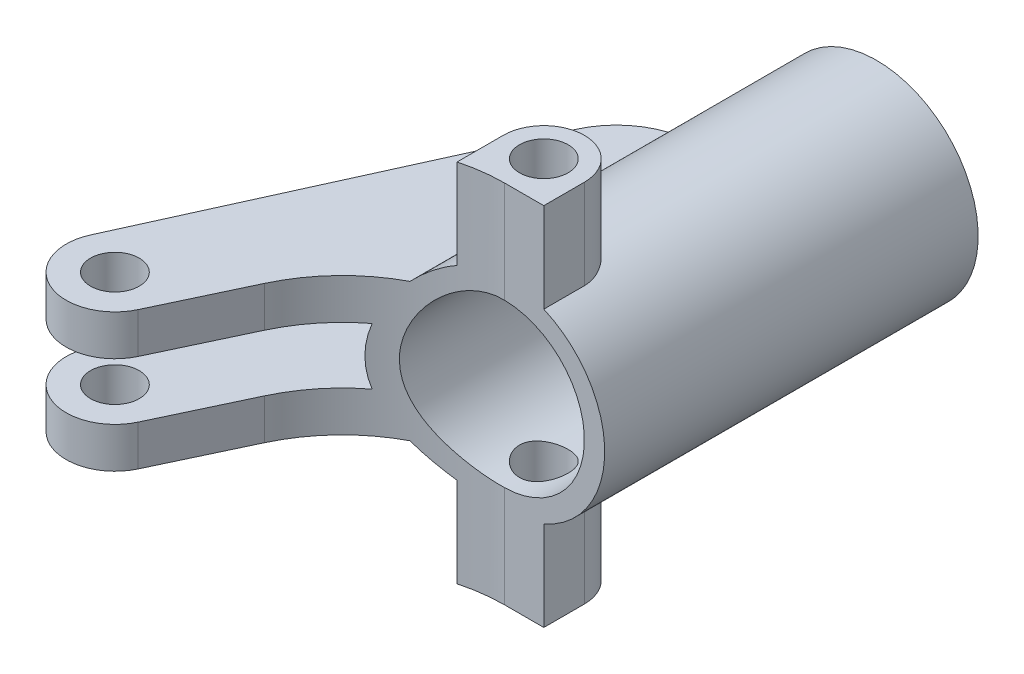
SolidWorks part; units mm, degrees
ref_plane "Alzado" through (0, 0, 0) normal (0, 0, 1) x (1, 0, 0)
ref_plane "Planta" through (0, 0, 0) normal (0, 1, 0) x (1, 0, 0)
ref_plane "Vista lateral" through (0, 0, 0) normal (1, 0, 0) x (0, 0, -1)
sketch "Croquis1" plane through (0, 0, 0) normal (0, 0, 1) x (1, 0, 0)
  circle A0 centre (0, 0) radius 6.25
  circle A1 centre (0, 0) radius 5
  dimension "D1" = 12.5
  dimension "D2" = 10
extrude "Saliente-Extruir1" add sketch "Croquis1" along normal blind 15
ref_plane "Plano1" through (0, 6.25, 0) normal (0, 1, 0) x (1, 0, 0)
ref_plane "Plano2" through (0, 11.25, 0) normal (0, 1, 0) x (1, 0, 0)
ref_plane "Plano3" through (0, -11.25, 0) normal (0, 1, 0) x (1, 0, 0)
sketch "Croquis2" plane through (0, 11.25, 0) normal (0, 1, 0) x (1, 0, 0)
  line L0 (0, -15) -> (0, -8.2224) construction
  line L1 (-6.25, -15) -> (6.25, -15) construction
  line L2 (-2.5, -15) -> (-2.5, -10)
  line L3 (-2.5, -10) -> (2.5, -10)
  line L4 (2.5, -10) -> (2.5, -15)
  line L5 (2.5, -15) -> (-2.5, -15)
  dimension "D1" = 5
  dimension "D2" = 5
extrude "Saliente-Extruir2" add sketch "Croquis2" against normal up to next
sketch "Croquis3" plane through (0, -11.25, 0) normal (0, 1, 0) x (1, 0, 0)
  line L0 (-2.5, -15) -> (2.5, -15) construction
  line L1 (2.5, -15) -> (2.5, -10) construction
  line L2 (-2.5, -10) -> (-2.5, -15) construction
  line L3 (2.5, -10) -> (-2.5, -10) construction
  line L4 (-2.5, -15) -> (2.5, -15)
  line L5 (2.5, -15) -> (2.5, -10)
  line L6 (-2.5, -10) -> (-2.5, -15)
  line L7 (2.5, -10) -> (-2.5, -10)
extrude "Saliente-Extruir3" add sketch "Croquis3" along normal up to next
sketch "Croquis4" plane through (0, 11.25, 0) normal (0, 1, 0) x (1, 0, 0)
  line L0 (-2.5, -12.5) -> (3.9489, -12.5) construction
  line L1 (-2.5, -10) -> (-2.5, -15) construction
  line L2 (0, -8.736) -> (0, -17.4365) construction
  circle A0 centre (0, -12.5) radius 1.5
  dimension "D1" = 3
extrude "Cortar-Extruir1" cut sketch "Croquis4" against normal up to surface (22.5 mm away) up to face at (0, -11.25, 12.5)
fillet "Redondeo1" radius 2.5 4 edges at (-2.5, -8.4891, 10) (2.5, -8.4891, 10) (-2.5, 8.4891, 10) (2.5, 8.4891, 10)
ref_plane "Plano4" through (-6.25, 0, 0) normal (-1, 0, 0) x (0, 0, 1)
ref_plane "Plano5" through (-13.75, 0, 0) normal (-1, 0, 0) x (0, 0, 1)
ref_plane "Plano6" through (0, 4.25, 0) normal (0, 1, 0) x (1, 0, 0)
ref_plane "Plano7" through (0, -4.25, 0) normal (0, 1, 0) x (1, 0, 0)
sketch "Croquis5" plane through (0, -4.25, 0) normal (0, 1, 0) x (1, 0, 0)
  line L0 (-6.25, -15) -> (-11.4459, -26.0332)
  line L1 (-6.25, 0) -> (-6.25, -15) construction
  line L2 (-16.8931, -23.5181) -> (-6.25, 0)
  line L3 (-6.25, -15) -> (-6.25, 0)
  arc A0 (-11.4459, -26.0332) -> (-16.8931, -23.5181) centre (-14.16, -24.755) cw
  circle A1 centre (-14.16, -24.755) radius 1.5
  circle A2 centre (0, -12.5) radius 1.5 construction
  dimension "D1" = 3
  dimension "D2" = 3
  dimension "D5" = 15
  dimension "D3" = 12.255
  dimension "D4" = 25.217
extrude "Saliente-Extruir4" add sketch "Croquis5" along normal blind 2.5 separate body
sketch "Croquis6" plane through (-6.25, 0, 0) normal (1, 0, 0) x (0, 0, -1)
  line L4 (-15, -4.25) -> (0, -4.25)
  line L5 (0, -4.25) -> (0, -1.75)
  line L6 (0, -1.75) -> (-15, -1.75)
  line L7 (-15, -1.75) -> (-15, -4.25)
  line L8 (-15, -4.25) -> (0, -4.25)
  line L9 (0, -4.25) -> (0, -1.75)
  line L10 (0, -1.75) -> (-15, -1.75)
  line L11 (-15, -1.75) -> (-15, -4.25)
  dimension "D1" = 0
extrude "Saliente-Extruir5" add sketch "Croquis6" along normal up to next
sketch "Croquis7" plane through (0, 4.25, 0) normal (0, 1, 0) x (1, 0, 0)
  line L0 (-11.4459, -26.0332) -> (-6.25, -15) construction
  line L1 (-6.25, 0) -> (-16.8931, -23.5181) construction
  line L2 (-11.4459, -26.0332) -> (-6.25, -15)
  line L3 (-6.25, 0) -> (-16.8931, -23.5181)
  line L4 (-6.25, -15) -> (-6.25, 0)
  arc A0 (-16.8931, -23.5181) -> (-11.4459, -26.0332) centre (-14.16, -24.755) ccw construction
  circle A1 centre (-14.16, -24.755) radius 1.5 construction
  arc A2 (-16.8931, -23.5181) -> (-11.4459, -26.0332) centre (-14.16, -24.755) ccw
  circle A3 centre (-14.16, -24.755) radius 1.5
extrude "Saliente-Extruir6" add sketch "Croquis7" against normal blind 2.5 separate body
sketch "Croquis8" plane through (-6.25, 0, 0) normal (1, 0, 0) x (0, 0, -1)
  line L4 (0, 4.25) -> (-15, 4.25)
  line L5 (-15, 4.25) -> (-15, 1.75)
  line L6 (-15, 1.75) -> (0, 1.75)
  line L7 (0, 1.75) -> (0, 4.25)
  line L8 (0, 4.25) -> (-15, 4.25)
  line L9 (-15, 4.25) -> (-15, 1.75)
  line L10 (-15, 1.75) -> (0, 1.75)
  line L11 (0, 1.75) -> (0, 4.25)
  dimension "D1" = 0
extrude "Saliente-Extruir7" add sketch "Croquis8" along normal up to surface (0.25 mm away)
fillet "Redondeo2" radius 5 1 edges at (-6.25, 3, 0)
fillet "Redondeo3" [suppressed] radius 5
fillet "Redondeo4" radius 10 1 edges at (-6.25, 3, 15)
sketch "Croquis9" plane through (0, 0, 0) normal (0, 0, -1) x (-1, 0, 0)
  circle A0 centre (0, 0) radius 6.25
  circle A1 centre (0, 0) radius 5
extrude "Saliente-Extruir8" [suppressed] add sketch "Croquis9" along normal blind 8
ref_plane "Plano8" through (0, 0, -8) normal (0, 0, -1) x (-1, 0, 0)
sketch "Croquis10" plane through (0, 0, -8) normal (0, 0, -1) x (-1, 0, 0)
  circle A0 centre (0, 0) radius 6.25
  circle A1 centre (0, 0) radius 5
extrude "Saliente-Extruir9" add sketch "Croquis10" against normal up to next
